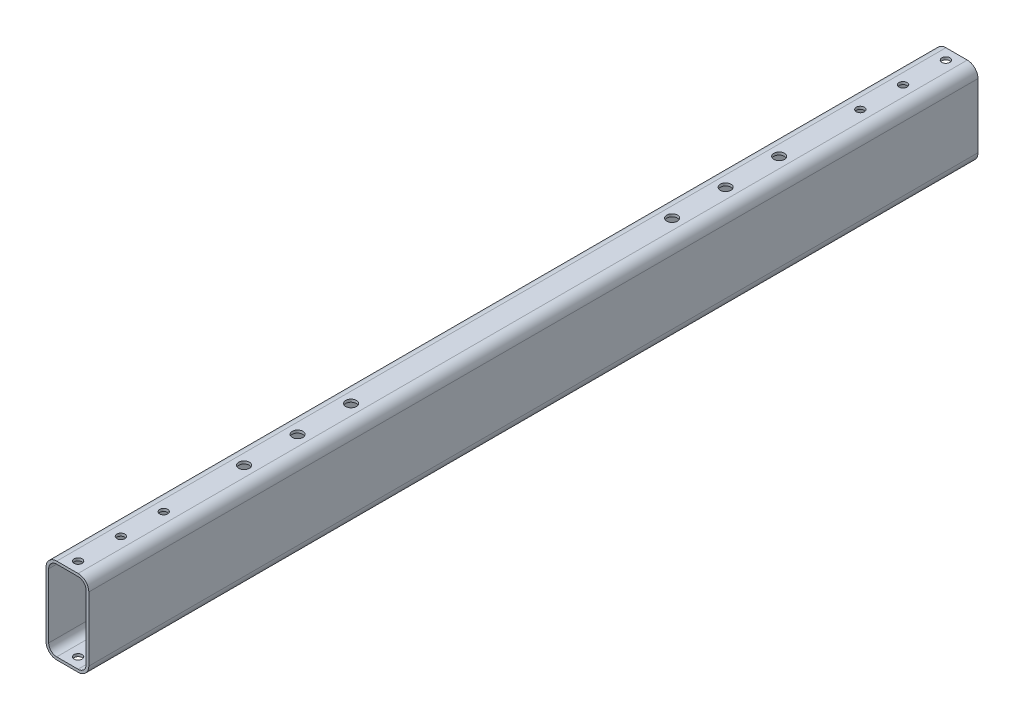
SolidWorks part; units mm, degrees
material "6061-T6 (SS)"
ref_plane "Front Plane" through (0, 0, 0) normal (0, 0, 1) x (1, 0, 0)
ref_plane "Top Plane" through (0, 0, 0) normal (0, 1, 0) x (1, 0, 0)
ref_plane "Right Plane" through (0, 0, 0) normal (1, 0, 0) x (0, 0, -1)
sketch "Sketch1" plane through (0, 0, 0) normal (0, 0, 1) x (1, 0, 0)
  line L1 (-6.35, -25.4) -> (6.35, -25.4)
  line L2 (-12.7, -19.05) -> (-12.7, 19.05)
  line L3 (-6.35, 25.4) -> (6.35, 25.4)
  line L4 (12.7, -19.05) -> (12.7, 19.05)
  line L5 (-12.7, -25.4) -> (12.7, 25.4) construction
  line L6 (-12.7, 25.4) -> (12.7, -25.4) construction
  arc A0 (-12.7, -19.05) -> (-6.35, -25.4) centre (-6.35, -19.05) ccw
  arc A1 (6.35, -25.4) -> (12.7, -19.05) centre (6.35, -19.05) ccw
  arc A2 (6.35, 25.4) -> (12.7, 19.05) centre (6.35, 19.05) cw
  arc A3 (-12.7, 19.05) -> (-6.35, 25.4) centre (-6.35, 19.05) cw
  point P0 (0, 0)
  dimension "D3" = 6.35
  dimension "D1" = 50.8
  dimension "D2" = 25.4
extrude "Extrude-Thin1" add sketch "Sketch1" along normal blind 527.685 thin thin type one direction reverse wall 1.5875
hole_wizard "3/16 (0.1875) Diameter Hole1" positions "3DSketch1" profile "Sketch3" hole size "3/16" standard "ANSI Inch" end condition through all
sketch3d "3DSketch1"
  line L1 (6.35, 25.4, 0) -> (-6.35, 25.4, 0) construction
  line L6 (0, 25.4, 527.685) -> (0, 25.4, 0) construction
  line L7 (6.35, 25.4, 527.685) -> (-6.35, 25.4, 527.685) construction
  point P57 (0, 25.4, 6.35)
  point P59 (0, 25.4, 31.75)
  point P61 (0, 25.4, 57.15)
  point P63 (0, 25.4, 495.935)
  point P65 (0, 25.4, 470.535)
  point P67 (0, 25.4, 521.335)
  dimension "D1" = 25.4
  dimension "D2" = 25.4
  dimension "D3" = 6.35
  dimension "D4" = 25.4
  dimension "D5" = 25.4
  dimension "D6" = 6.35
sketch "Sketch3" plane through (0, 25.4, 521.335) normal (1, 0, 0) x (0, 0, 1)
  line L0 (0, 0) -> (0, 50.8)
  line L1 (0, 50.8) -> (2.3812, 50.8)
  line L2 (2.3812, 50.8) -> (2.3812, 0)
  line L5 (2.3812, 0) -> (0, 0)
  line L11 (0, -6.35) -> (0, 107.95) construction
  dimension "Thru Hole Dia." = 4.7625
  dimension "Thru Hole Depth" = 50.8
hole_wizard "3/16 (0.195) Diameter Hole1" positions "Sketch4" profile "Sketch5" hole size "3/16" standard "ANSI Inch" end condition up to next
sketch "Sketch4" plane through (0, -25.4, 0) normal (0, -1, 0) x (-1, 0, 0)
  point P3 (3.175, -114.3903)
  point P6 (-3.175, -139.7903)
  point P9 (3.175, -165.1903)
  point P15 (-3.175, -393.7903)
  point P18 (3.175, -368.3903)
  point P21 (-3.175, -342.9903)
  point P29 (-3.175, -190.5903)
sketch "Sketch5" plane through (-3.175, -25.4, 114.3903) normal (1, 0, 0) x (0, 0, -1)
  line L0 (0, 0) -> (0, 1.5875)
  line L1 (0, 1.5875) -> (2.4765, 1.5875)
  line L2 (2.4765, 1.5875) -> (2.4765, 0)
  line L5 (2.4765, 0) -> (0, 0)
  line L11 (0, -6.35) -> (0, 107.95) construction
  dimension "Thru Hole Dia." = 4.953
  dimension "Thru Hole Depth" = 1.5875
hole_wizard "1/4 (0.25) Diameter Hole1" positions "Sketch6" profile "Sketch7" hole size "1/4" standard "ANSI Inch"
sketch "Sketch6" plane through (0, 25.4, 0) normal (0, 1, 0) x (1, 0, 0)
  point P0 (0, -105.3102)
  point P3 (0, -137.0602)
  point P6 (0, -168.8102)
  point P9 (0, -422.835)
  point P12 (0, -391.085)
  point P15 (0, -359.335)
sketch "Sketch7" plane through (0, 25.4, 105.3102) normal (1, 0, 0) x (0, 0, 1)
  line L0 (0, 0) -> (0, 27.3077)
  line L1 (0, 27.3077) -> (3.175, 25.4)
  line L2 (3.175, 25.4) -> (3.175, 0)
  line L5 (3.175, 0) -> (0, 0)
  line L10 (0, 27.3077) -> (-3.175, 25.4) construction
  line L11 (0, -6.35) -> (0, 107.95) construction
  dimension "Hole Dia." = 6.35
  dimension "Hole Depth" = 25.4
  dimension "Drill Angle" = 118
